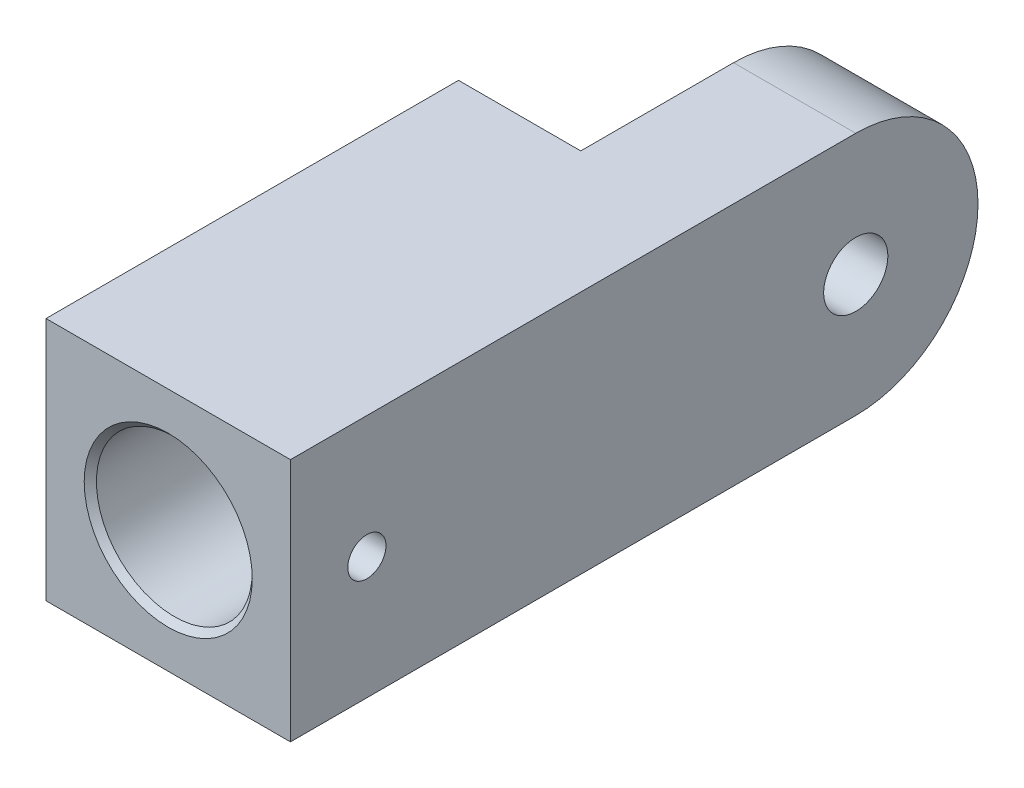
SolidWorks part; units mm, degrees
material "6063-T6"
ref_plane "Front Plane" through (0, 0, 0) normal (0, 0, 1) x (1, 0, 0)
ref_plane "Top Plane" through (0, 0, 0) normal (0, 1, 0) x (1, 0, 0)
ref_plane "Right Plane" through (0, 0, 0) normal (1, 0, 0) x (0, 0, -1)
sketch "Sketch1" plane through (0, 0, 0) normal (0, 0, 1) x (1, 0, 0)
  line L1 (8, 8) -> (-8, 8)
  line L2 (8, 8) -> (8, -8)
  line L3 (8, -8) -> (-8, -8)
  line L4 (-8, 8) -> (-8, -8)
  line L5 (8, 8) -> (-8, -8) construction
  line L6 (8, -8) -> (-8, 8) construction
  point P0 (0, 0)
  dimension "D1" = 16
  dimension "D2" = 16
extrude "Base" add sketch "Sketch1" along normal blind 45
sketch "Sketch3" plane through (0, 0, 0) normal (1, 0, 0) x (0, 0, -1)
  line L0 (-45, -8) -> (0, -8) construction
  line L1 (-18, 8) -> (1.9274, 8)
  line L2 (-18, 8) -> (-18, -8)
  line L3 (-18, -8) -> (1.9274, -8)
  line L4 (1.9274, 8) -> (1.9274, -8)
  line L5 (-45, 8) -> (0, 8) construction
  line L6 (0, -8) -> (0, 8) construction
  circle A0 centre (-8, 0) radius 8
  dimension "D1" = 18
extrude "SlotForAnotherPart" cut sketch "Sketch3" against normal through all contours A0 L1 L2 L3 | A0 | A0 L3 L4 L1 region at (0, 7.8113, 13) region at (0, 7.8117, 3.0363) region at (0, 0, 8)
extrude "ChamferForSlot" cut sketch "Sketch3<3>" along normal through all contours A0 L3 L4 L1 region at (0, 7.8117, 3.0363)
sketch "Sketch3<3>" plane through (0, 0, 0) normal (1, 0, 0) x (0, 0, -1) same geometry as "Sketch3"
hole_wizard "M5x0.8 Tapped Hole for SlotScrew" positions "Sketch4" profile "Sketch5" tap size "M5x0.8" standard "ANSI Metric"
sketch "Sketch4" plane through (8, 0, 0) normal (1, 0, 0) x (0, 0, -1)
  point P0 (-8, 0)
sketch "Sketch5" plane through (8, 0, 8) normal (0, 1, 0) x (0, 0, -1)
  line L0 (0, 0) -> (0, 12.4)
  line L1 (0, 12.4) -> (2.1, 11.1382)
  line L2 (2.1, 11.1382) -> (2.1, 0)
  line L5 (2.1, 0) -> (0, 0)
  line L10 (0, 12.4) -> (-2.1, 11.1382) construction
  line L11 (0, -6.35) -> (0, 107.95) construction
  dimension "Tap Drill Dia." = 4.2
  dimension "Tap Drill Depth" = 12.4
  dimension "Drill Angle" = 118
cosmetic thread "Hole Thread1" parameters "D1"=8, "D2"=5
hole_wizard "M3x0.5 Tapped Hole for Rod Fixing" positions "Sketch7" profile "Sketch8" tap size "M3x0.5" standard "ANSI Metric"
sketch "Sketch7" plane through (8, 0, 0) normal (1, 0, 0) x (0, 0, -1)
  line L0 (-45, -8) -> (-45, 8) construction
  point P0 (-40, 0)
  dimension "D1" = 5
sketch "Sketch8" plane through (8, 0, 40) normal (0, 1, 0) x (0, 0, -1)
  line L0 (0, 0) -> (0, 7.5)
  line L1 (0, 7.5) -> (1.25, 6.7489)
  line L2 (1.25, 6.7489) -> (1.25, 0)
  line L5 (1.25, 0) -> (0, 0)
  line L10 (0, 7.5) -> (-1.25, 6.7489) construction
  line L11 (0, -6.35) -> (0, 107.95) construction
  dimension "Tap Drill Dia." = 2.5
  dimension "Tap Drill Depth" = 7.5
  dimension "Drill Angle" = 118
cosmetic thread "Hole Thread2" parameters "D1"=3.1588, "D2"=3
hole_wizard "Ø10.2 (10.2) Rod Hole" positions "Sketch9" profile "Sketch10" hole size "Ø10.2" standard "ANSI Metric"
sketch "Sketch9" plane through (0, 0, 45) normal (0, 0, 1) x (1, 0, 0)
  point P0 (0, 0)
sketch "Sketch10" plane through (0, 0, 45) normal (1, 0, 0) x (0, -1, 0)
  line L0 (0, 0) -> (0, 15)
  line L1 (0, 15) -> (5.1, 11.9356)
  line L2 (5.1, 11.9356) -> (5.1, 0.4)
  line L3 (5.1, 0.4) -> (5.5, 0)
  line L5 (5.5, 0) -> (0, 0)
  line L6 (-5.1, 0.4) -> (-5.5, 0) construction
  line L10 (0, 15) -> (-5.1, 11.9356) construction
  line L11 (0, -6.35) -> (0, 107.95) construction
  dimension "Hole Dia." = 10.2
  dimension "Hole Depth" = 15
  dimension "Near C'Sink Dia." = 11
  dimension "Near C'Sink Angle" = 90
  dimension "Drill Angle" = 118
equation "\"D2@Sketch1\"=\"D1@Sketch1\""
